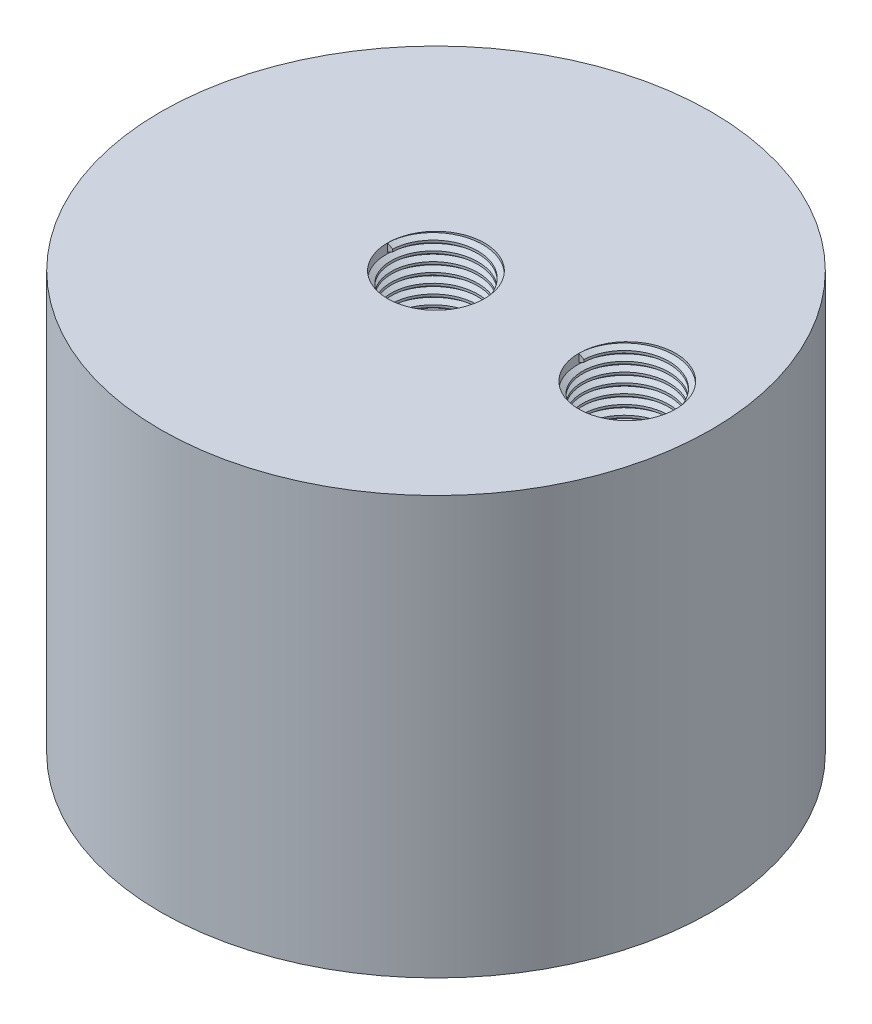
SolidWorks part; units mm, degrees
ref_plane "Спереди" through (0, 0, 0) normal (0, 0, 1) x (1, 0, 0)
ref_plane "Сверху" through (0, 0, 0) normal (0, 1, 0) x (1, 0, 0)
ref_plane "Справа" through (0, 0, 0) normal (1, 0, 0) x (0, 0, -1)
sketch "Эскиз1" plane through (0, 0, 0) normal (0, 0, 1) x (1, 0, 0)
  line L0 (0, 0) -> (0, 64.3029) construction
  line L33 (30, 28.7946) -> (30, 26.2946)
  line L34 (30, 26.2946) -> (28.4, 26.2946)
  line L35 (28.4, 26.2946) -> (28.4, 18.2946)
  line L37 (8, 58.6338) -> (2, 62.0979)
  line L38 (2, 62.0979) -> (37.4277, 62.0979)
  line L40 (28.4, 18.2946) -> (37.4277, 18.2946)
  line L41 (37.4277, 18.2946) -> (37.4277, 62.0979)
  line L42 (8, 58.6338) -> (8.3476, 52.0019)
  line L43 (8.3476, 52.0019) -> (10.7476, 49.4019)
  line L44 (8, 58.6338) -> (8, 51.4355) construction
  line L45 (10.7476, 49.4019) -> (10.9672, 43.1119)
  line L46 (10.7476, 49.4019) -> (10.7476, 37.0019) construction
  line L50 (12.2182, 33.9946) -> (19.2771, 33.9946) construction
  line L51 (12.2182, 33.9946) -> (16.6302, 29.9946)
  line L53 (30, 28.7946) -> (30, 29.9946)
  line L54 (16.6302, 29.9946) -> (30, 29.9946)
  line L55 (11.9976, 38.5019) -> (11.9976, 41.6565) construction
  line L56 (11.9976, 40.3132) -> (12.2182, 33.9946)
  arc A0 (11.9976, 40.3132) -> (10.9672, 43.1119) centre (11.33, 41.6565) ccw
  point P8 (10.9083, 44.8)
  point P11 (11.33, 41.6565)
  point P15 (0, 61.8065)
  point P17 (11.9976, 38.5019)
  dimension "D5" = 16
  dimension "D14" = 3
  dimension "D3" = 2.6
  dimension "D4" = 3
  dimension "D6" = 60
  dimension "D8" = 4
  dimension "D9" = 2
  dimension "D10" = 2.4
  dimension "D12" = 20.15
  dimension "D13" = 11.33
  dimension "D15" = 1.25
  dimension "D16" = 10.9
  dimension "D17" = 4
  dimension "D18" = 2
  dimension "D20" = 2.5
  dimension "D21" = 8
  dimension "D23" = 1.6
  dimension "D26" = 6.29
revolve "Повернуть1" add sketch "Эскиз1" angle 360 about L0 reverse direction yes
sketch "Эскиз2" plane through (0, 62.0979, 0) normal (0, 1, 0) x (1, 0, 0)
  circle A0 centre (0, 0) radius 2 construction
  circle A1 centre (0, 0) radius 37.4277
  circle A2 centre (0, 0) radius 37.4277
  circle A3 centre (0, 0) radius 2
  dimension "D1" = 0
extrude "Бобышка-Вытянуть1" add sketch "Эскиз2" along normal blind 13
sketch "Эскиз3" plane through (0, 75.0979, 0) normal (0, 1, 0) x (1, 0, 0)
  circle A0 centre (0, 0) radius 6.579
  dimension "D1" = 13.158
extrude "Вырез-Вытянуть1" cut sketch "Эскиз3" against normal blind 13
thread "Резьба1" pitch 1.27 method extrude profile "Профиль резьбы1" start angle 0, offset 0, length 10, pitch 1.27, diameter 13.158
ref_plane "Плоскость1" through (-6.579, 75.0979, 0) normal (0, 0, 1) x (-1, 0, 0)
sketch "Профиль резьбы1" plane through (-6.579, 75.0979, 0) normal (0, 0, 1) x (-1, 0, 0)
  line L0 (0, 0) -> (0, 1.27) construction
  line L11 (0, 0) -> (0, 1.1112)
  line L12 (0, 1.1112) -> (-0.6874, 0.7144)
  line L13 (-0.6874, 0.7144) -> (-0.6874, 0.3969)
  line L15 (-0.6874, 0.3969) -> (0, 0)
  line L17 (-0.6874, 0.5556) -> (0, 0.5556) construction
  point P2 (0, 0)
  dimension "Pitch" = 1.27
  dimension "Profile_Angle" = 60
  dimension "Profile_Land" = 0.3175
  dimension "Profile_Height" = 0.6874
sketch "Эскиз6" plane through (0, 0, 0) normal (0, 0, 1) x (1, 0, 0)
  line L0 (10.9672, 43.1119) -> (-10.9672, 43.1119) construction
  line L1 (11.408, 41.4874) -> (26, 56.5979)
  line L2 (26, 56.5979) -> (26, 75.0979)
  line L3 (37.4277, 75.0979) -> (-37.4277, 75.0979) construction
  line L5 (10.9672, 43.1119) -> (-10.9672, 43.1119) construction
  point P0 (10.9672, 39.9874)
  point P1 (0, 0)
  point P2 (0, 0)
  point P8 (0, 75.0979)
  point P11 (10.9672, 43.6289)
  point P12 (10.9672, 43.1119)
  dimension "D1" = 44
  dimension "D2" = 26
  dimension "D3" = 18.5
sketch "Эскиз7" plane through (0, 75.0979, 0) normal (0, 1, 0) x (1, 0, 0)
  circle A0 centre (26, 0) radius 1.5
  dimension "D1" = 3
sweep "Вырез-По траектории5" cut profiles "Эскиз7" path "Эскиз6"
sketch "Эскиз26" plane through (0, 75.0979, 0) normal (0, 1, 0) x (1, 0, 0)
  circle A0 centre (26, 0) radius 6.579
  dimension "D1" = 13.158
extrude "Вырез-Вытянуть2" cut sketch "Эскиз26" against normal blind 13
thread "Резьба2" pitch 1.27 method extrude profile "Профиль резьбы2" start angle 0, offset 0, length 10, pitch 1.27, diameter 13.158
ref_plane "Плоскость2" through (19.421, 75.0979, 0) normal (0, 0, 1) x (-1, 0, 0)
sketch "Профиль резьбы2" plane through (19.421, 75.0979, 0) normal (0, 0, 1) x (-1, 0, 0)
  line L0 (0, 0) -> (0, 1.27) construction
  line L11 (0, 0) -> (0, 1.1112)
  line L12 (0, 1.1112) -> (-0.6874, 0.7144)
  line L13 (-0.6874, 0.7144) -> (-0.6874, 0.3969)
  line L15 (-0.6874, 0.3969) -> (0, 0)
  line L17 (-0.6874, 0.5556) -> (0, 0.5556) construction
  point P2 (0, 0)
  dimension "Pitch" = 1.27
  dimension "Profile_Angle" = 60
  dimension "Profile_Land" = 0.3175
  dimension "Profile_Height" = 0.6874
